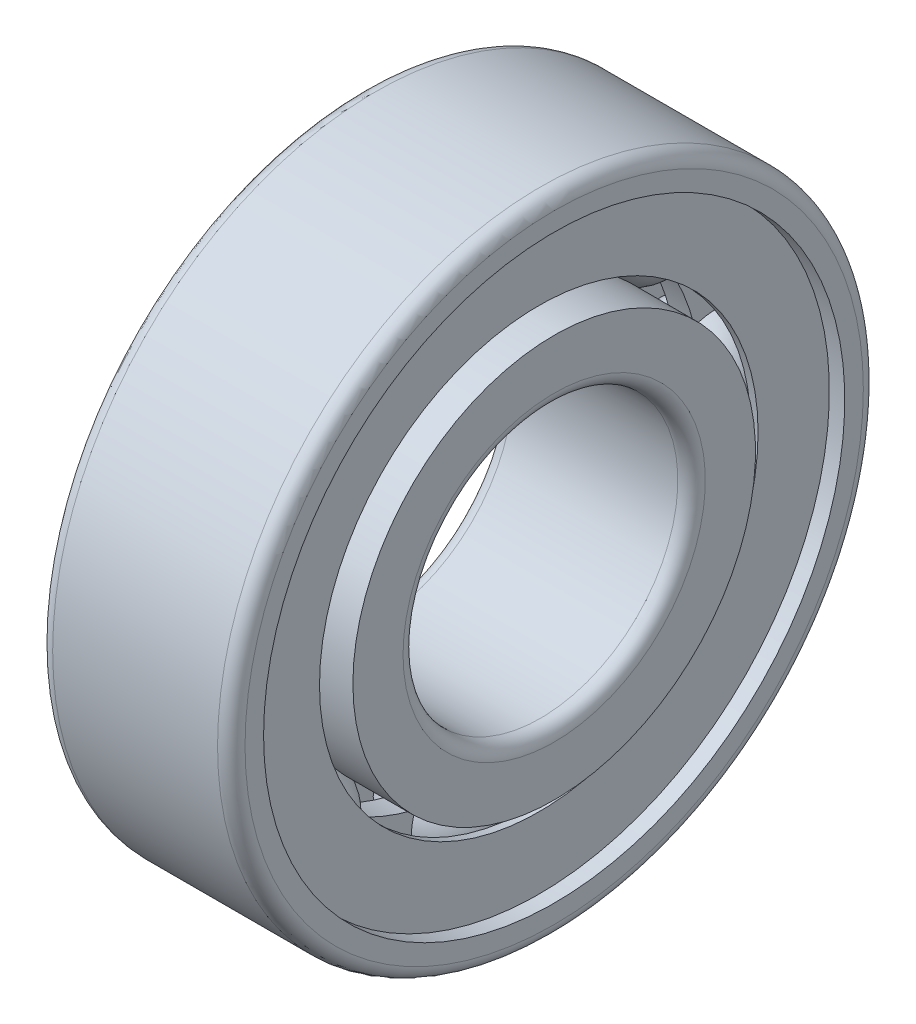
SolidWorks part; units mm, degrees
ref_plane "基准面1" through (0, 0, 0) normal (0, 0, 1) x (1, 0, 0)
ref_plane "基准面2" through (0, 0, 0) normal (0, 1, 0) x (1, 0, 0)
ref_plane "基准面3" through (0, 0, 0) normal (1, 0, 0) x (0, 0, -1)
sketch "尺寸草图" plane through (0, 0, 0) normal (0, 0, 1) x (1, 0, 0)
  point P0 (0, -75.4307)
  point P1 (7.938, -75.4307)
  point P2 (0, 50.7088)
  point P3 (20, 50.7088)
  point P4 (47, 50.7088)
  point P5 (14, 50.7088)
  point P6 (0, -10.9899)
  point P7 (29.3, -10.9899)
  point P8 (41.6, -10.9899)
  point P9 (1, -10.9899)
  point P10 (8, -75.4307)
  dimension "d" = 20
  dimension "DD" = 47
  dimension "B" = 14
  dimension "内圈外径DD2" = 29.3
  dimension "防尘圈径D3" = 41.6
  dimension "r" = 1
  dimension "球径DW" = 7.938
  dimension "球数Z" = 8
sketch "草图2" plane through (0, 0, 0) normal (0, 0, 1) x (1, 0, 0)
  line L0 (-12.4206, 0) -> (9.8128, 0) construction
  line L1 (0, 0) -> (0, 37.3563) construction
  line L2 (-5.5681, 17.9) -> (6.1049, 17.9) construction
  line L3 (-0.8732, 18.9915) -> (0.8732, 18.9915)
  line L4 (-0.8732, 18.9915) -> (-0.8732, 16.8085)
  line L5 (-0.8732, 16.8085) -> (0.8732, 16.8085)
  line L6 (0.8732, 18.9915) -> (0.8732, 16.8085)
  dimension "D1" = 1.7464
  dimension "D2" = 0.8732
  dimension "D3" = 2.1829
  dimension "D4" = 1.0915
  dimension "D5" = 17.9
revolve "基体-旋转" add sketch "草图2" angle 360 about L0
sketch "草图3" plane through (0, 0, 0) normal (0, 0, 1) x (1, 0, 0)
  line L0 (-5.5681, 17.9) -> (6.1049, 17.9) construction
  line L1 (-5.5681, 17.9) -> (6.1049, 17.9) construction
  line L2 (-12.4206, 0) -> (9.8128, 0) construction
  line L3 (-12.4206, 0) -> (9.8128, 0) construction
  line L4 (0, 0) -> (0, 37.3563) construction
  line L5 (0, 0) -> (0, 37.3563) construction
  line L6 (-4.3659, 17.9) -> (4.3659, 17.9)
  arc A0 (-4.3659, 17.9) -> (4.3659, 17.9) centre (0, 17.9) ccw
  dimension "Dwww" = 8.7318
  dimension "D2" = 4.3659
revolve "凸台-旋转1" add sketch "草图3" angle 360 about L1
pattern_circular "阵列(圆周)1" count 8 over 360 about axis through (-12.4206, 0, 0) along (1, 0, 0) of "凸台-旋转1"
sketch "草图4" plane through (0, 0, 0) normal (0, 0, 1) x (1, 0, 0)
  line L0 (0, 0) -> (8.1272, 0) construction
  line L1 (-12.4206, 0) -> (9.8128, 0) construction
  line L3 (-0.8732, 18.9915) -> (0.8732, 18.9915) construction
  line L4 (-4.3659, 23.3574) -> (4.3659, 23.3574)
  line L5 (-4.3659, 23.3574) -> (-4.3659, 18.9915)
  line L6 (-4.3659, 18.9915) -> (4.3659, 18.9915)
  line L7 (4.3659, 23.3574) -> (4.3659, 18.9915)
revolve "切除-旋转1" cut sketch "草图4" angle 360 about L0
sketch "草图5" plane through (0, 0, 0) normal (0, 0, 1) x (1, 0, 0)
  line L0 (0, 0) -> (8.2665, 0) construction
  line L1 (-12.4206, 0) -> (9.8128, 0) construction
  line L2 (-0.8732, 16.8085) -> (0.8732, 16.8085) construction
  line L3 (-4.3659, 16.8085) -> (4.3659, 16.8085)
  line L4 (-4.3659, 16.8085) -> (-4.3659, 12.4426)
  line L5 (-4.3659, 12.4426) -> (4.3659, 12.4426)
  line L6 (4.3659, 16.8085) -> (4.3659, 12.4426)
revolve "切除-旋转2" cut sketch "草图5" angle 360 about L0
sketch "草图6" plane through (0, 0, 0) normal (0, 0, 1) x (1, 0, 0)
  line L0 (0, 0) -> (5.5439, 0) construction
  line L1 (-12.4206, 0) -> (9.8128, 0) construction
  line L2 (0, 0) -> (0, 11.4011) construction
  line L3 (-5.5681, 17.9) -> (6.1049, 17.9) construction
  line L4 (-5.5681, 17.9) -> (6.1049, 17.9) construction
  line L5 (-3.969, 17.9) -> (3.969, 17.9)
  arc A0 (-3.969, 17.9) -> (3.969, 17.9) centre (0, 17.9) ccw
  dimension "Dw" = 7.938
revolve "凸台-旋转2" add sketch "草图6" angle 360 about L4
pattern_circular "阵列(圆周)2" count 8 over 360 about axis through (-12.4206, 0, 0) along (1, 0, 0) of "凸台-旋转2"
sketch "草图7" plane through (0, 0, 0) normal (0, 0, 1) x (1, 0, 0)
  line L0 (0, 0) -> (6.6488, 0) construction
  line L1 (0, 0) -> (0, 16.8954) construction
  line L2 (-6, 23.5) -> (6, 23.5)
  line L3 (-7, 22.5) -> (-7, 21.15)
  line L4 (-7, 21.15) -> (-2.2608, 21.15)
  line L5 (7, 22.5) -> (7, 21.15)
  line L6 (2.2608, 21.15) -> (5.3448, 21.15)
  line L7 (5.88, 21.15) -> (7, 21.15)
  line L8 (5.3448, 20.8) -> (5.88, 20.8)
  line L9 (5.3448, 20.8) -> (5.3448, 21.15)
  line L11 (5.88, 20.8) -> (5.88, 21.15)
  arc A0 (-6, 23.5) -> (-7, 22.5) centre (-6, 22.5) ccw
  arc A1 (6, 23.5) -> (7, 22.5) centre (6, 22.5) cw
  arc A2 (3.816, 18.9915) -> (-3.816, 18.9915) centre (0, 17.9) ccw construction
  arc A3 (2.2783, 21.15) -> (0, 13.931) centre (0, 17.9) ccw construction
  arc A4 (2.2608, 21.15) -> (-2.2608, 21.15) centre (0, 17.9) ccw
  point P10 (-7, 23.5)
  point P13 (7, 23.5)
  dimension "R" = 1
  dimension "D1" = 0.01
  dimension "D2" = 42.3
  dimension "D" = 47
  dimension "D3" = 7
  dimension "B" = 14
  dimension "D4" = 0.5352
  dimension "D5" = 41.6
  dimension "D6" = 1.12
revolve "凸台-旋转3" add sketch "草图7" angle 360 about L0
sketch "草图8" plane through (0, 0, 0) normal (0, 0, 1) x (1, 0, 0)
  line L0 (-12.4206, 0) -> (9.8128, 0) construction
  line L1 (-12.4206, 0) -> (9.8128, 0) construction
  line L2 (7, 22.5) -> (7, 21.15) construction
  line L3 (-7, 14.65) -> (-2.2608, 14.65)
  line L4 (-7, 14.65) -> (-7, 11)
  line L5 (-6, 10) -> (6, 10)
  line L6 (7, 14.65) -> (7, 11)
  line L7 (-7, 22.5) -> (-7, 21.15) construction
  line L8 (2.2608, 14.65) -> (7, 14.65)
  arc A0 (-7, 11) -> (-6, 10) centre (-6, 11) ccw
  arc A1 (6, 10) -> (7, 11) centre (6, 11) ccw
  arc A2 (-3.816, 16.8085) -> (3.816, 16.8085) centre (0, 17.9) ccw construction
  arc A3 (-3.816, 16.8085) -> (3.816, 16.8085) centre (0, 17.9) ccw construction
  arc A4 (-2.2608, 14.65) -> (2.2608, 14.65) centre (0, 17.9) ccw
  dimension "D1" = 1
  dimension "DD" = 20
  dimension "D2" = 0.01
  dimension "DD2" = 29.3
revolve "凸台-旋转4" add sketch "草图8" angle 360 about L1
sketch "草图10" plane through (0, 0, 0) normal (0, 0, 1) x (1, 0, 0)
  line L0 (5.3448, 21.15) -> (5.3448, -21.15) construction
  line L1 (5.88, 20.8) -> (5.3448, 20.8)
  line L2 (5.88, 20.8) -> (5.88, 15.9598)
  line L3 (5.88, 15.9598) -> (5.3448, 15.9598)
  line L4 (5.3448, 20.8) -> (5.3448, 15.9598)
  line L5 (2.2608, 14.65) -> (7, 14.65) construction
  line L6 (0, 0) -> (-5.3515, 0) construction
  line L7 (-12.4206, 0) -> (9.8128, 0) construction
  dimension "D1" = 1.3098
revolve "凸台-旋转5" add sketch "草图10" angle 360 about L6
sketch "草图11" plane through (0, 0, 0) normal (1, 0, 0) x (0, 0, -1)
  circle A0 centre (0, 0) radius 23.5
  circle A1 centre (0, 0) radius 23.5 construction
extrude "切除-拉伸1" cut sketch "草图11" against normal blind 10
mirror "镜向所有1" about plane through (0, 0, 0) normal (1, 0, 0) of bodies 109
equation "\"D5@草图7\" = \"防尘圈径D3@尺寸草图\""
equation "\"Z@阵列(圆周)1\"=\"球数Z@尺寸草图\" "
equation "\"Dw@草图6\"=\"球径DW@尺寸草图\""
equation "\"DD@草图8\"=\"d@尺寸草图\""
equation "\"D@草图7\"=\"DD@尺寸草图\""
equation "\"B@草图7\"=\"B@尺寸草图\" "
equation "\"DD2@草图8\"=\"内圈外径DD2@尺寸草图\""
equation "\"R@草图7\"=\"r@尺寸草图\""
equation "\"D3@草图2\" = 0.25*\"Dwww@草图3\""
equation "\"D4@草图2\" = \"D3@草图2\"/2"
equation "\"Dwww@草图3\" = 1.1*\"Dw@草图6\""
equation "\"D2@草图3\" = 0.5*\"Dwww@草图3\""
equation "\"D1@草图2\" = 0.2*\"Dwww@草图3\""
equation "\"D2@草图2\" = 0.5*\"D1@草图2\""
equation "\"切除位置@草图4\" = \"Dwww@草图3\"/2"
equation "\"D1@阵列(圆周)2\" = \"Z@阵列(圆周)1\""
equation "\"D3@草图7\" = \"B@草图7\" / 2"
equation "\"D1@草图8\" = \"R@草图7\""
equation "\"D2@草图7\" = 0.9*\"D@草图7\""
equation "\"D5@草图2\" = 0.25* ( \"D2@草图7\" + \"DD2@草图8\" )  "
equation "\"D6@草图7\" = 0.08 * \"B@草图7\""
equation "\"D1@草图10\" = 0.15*\"Dwww@草图3\""
